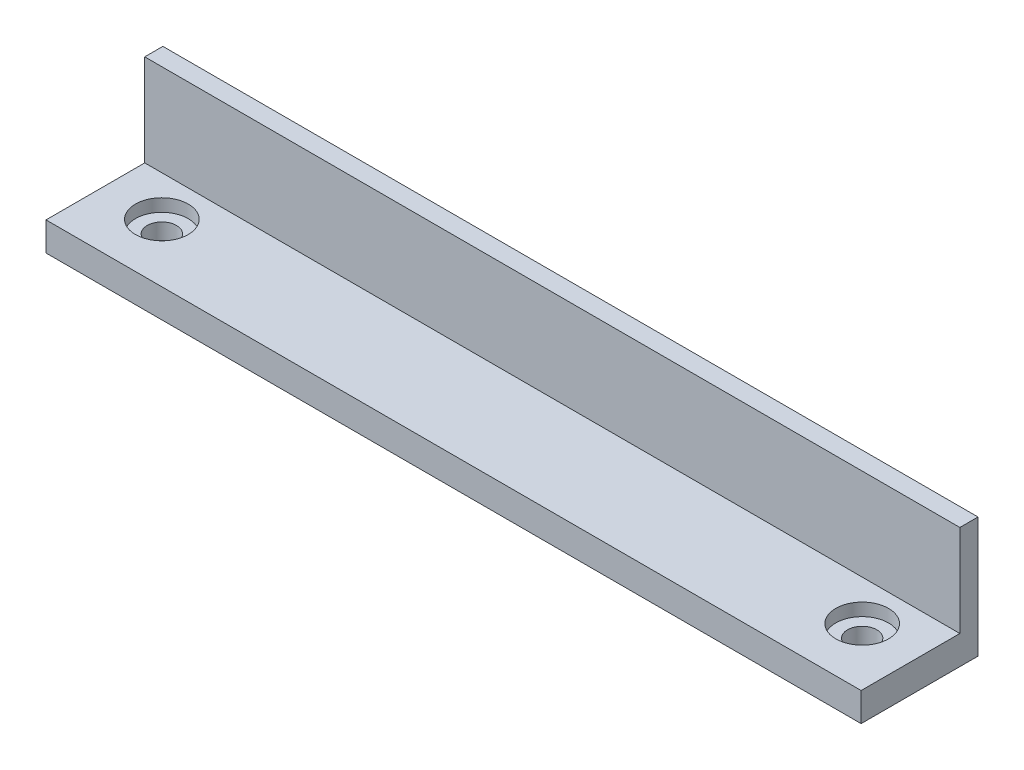
SolidWorks part; units mm, degrees
ref_plane "Front Plane" through (0, 0, 0) normal (0, 0, 1) x (1, 0, 0)
ref_plane "Top Plane" through (0, 0, 0) normal (0, 1, 0) x (1, 0, 0)
ref_plane "Right Plane" through (0, 0, 0) normal (1, 0, 0) x (0, 0, -1)
sketch "Sketch1" plane through (0, 0, 0) normal (0, 1, 0) x (1, 0, 0)
  line L0 (-71, 7.02) -> (71, 7.02)
  line L1 (-71, -10.18) -> (71, -10.18)
  line L2 (-71, -10.18) -> (-71, 10.18)
  line L3 (-71, 10.18) -> (71, 10.18)
  line L4 (71, -10.18) -> (71, 10.18)
  line L5 (-71, -10.18) -> (71, 10.18) construction
  line L6 (-71, 10.18) -> (71, -10.18) construction
  line L7 (0, 18.105) -> (0, -20.0728) construction
  circle A0 centre (61, 0) radius 2.55
  circle A1 centre (61, 0) radius 4.6
  circle A2 centre (-61, 0) radius 2.55
  circle A3 centre (-61, 0) radius 4.6
  point P0 (0, 0)
  dimension "D4" = 10
  dimension "D5" = 10.18
  dimension "D6" = 5.1
  dimension "D7" = 9.2
  dimension "D1" = 142
  dimension "D2" = 20.36
  dimension "D3" = 3.16
extrude "Boss-Extrude1" add sketch "Sketch1" along normal blind 5 contours L1 L4 L0 L2 A1 A3 | L0 L4 L3 L2 | A3 A2 | A1 A0 region at (0, 0, -8.6) region at (0, 0, 1.671) region at (56.5301, 0, 0) region at (-65.4699, 0, 0)
extrude "Boss-Extrude2" add sketch "Sketch1<3>" along normal blind 16 from surface contours L0 L4 L3 L2 region at (0, 0, -8.6) starting at face at (0, 5, 0)
sketch "Sketch1<3>" plane through (0, 0, 0) normal (0, 1, 0) x (1, 0, 0) same geometry as "Sketch1"
extrude "Cut-Extrude1" cut sketch "Sketch1<5>" against normal blind 2.2 from surface contours A3 A2 | A1 A0 region at (56.5301, 0, 0) region at (-65.4699, 0, 0) starting at face at (-61, 5, 2.55)
sketch "Sketch1<5>" plane through (0, 0, 0) normal (0, 1, 0) x (1, 0, 0) same geometry as "Sketch1"
